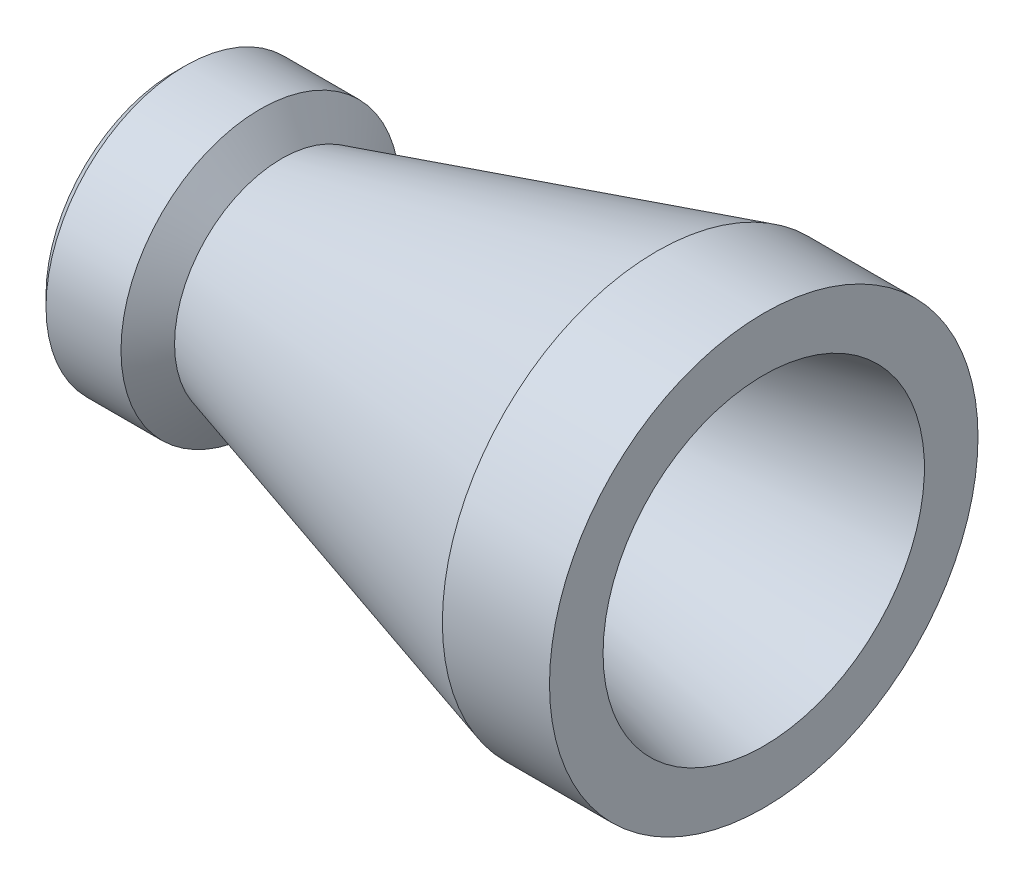
SolidWorks part; units mm, degrees
ref_plane "前基準面" through (0, 0, 0) normal (0, 0, 1) x (1, 0, 0)
ref_plane "上基準面" through (0, 0, 0) normal (0, 1, 0) x (1, 0, 0)
ref_plane "右基準面" through (0, 0, 0) normal (1, 0, 0) x (0, 0, -1)
sketch "草圖1" plane through (0, 0, 0) normal (0, 0, 1) x (1, 0, 0)
  line L0 (0, 0) -> (65.2536, 0) construction
  line L1 (0, 5) -> (0, 12)
  line L2 (1, 13) -> (8, 13)
  line L3 (8, 13) -> (10, 10)
  line L4 (10, 10) -> (45, 20)
  line L5 (45, 20) -> (55, 20)
  line L6 (55, 20) -> (55, 15)
  line L7 (55, 15) -> (23.5568, 7.8538)
  line L8 (22, 5.9035) -> (22, 5)
  line L9 (22, 5) -> (0, 5)
  line L10 (0, 0) -> (0, 26.747) construction
  line L11 (0, 12) -> (1, 13)
  arc A0 (22, 5.9035) -> (23.5568, 7.8538) centre (24, 5.9035) cw
  point P5 (0, 13)
  point P15 (22, 7.5)
  dimension "D7" = 2
  dimension "D1" = 20
  dimension "D2" = 10
  dimension "D3" = 2
  dimension "D4" = 10
  dimension "D5" = 30
  dimension "D6" = 15
  dimension "D8" = 10
  dimension "D9" = 22
  dimension "D10" = 55
  dimension "D11" = 40
  dimension "D12" = 26
revolve "旋轉1" add sketch "草圖1" angle 360 about L0
